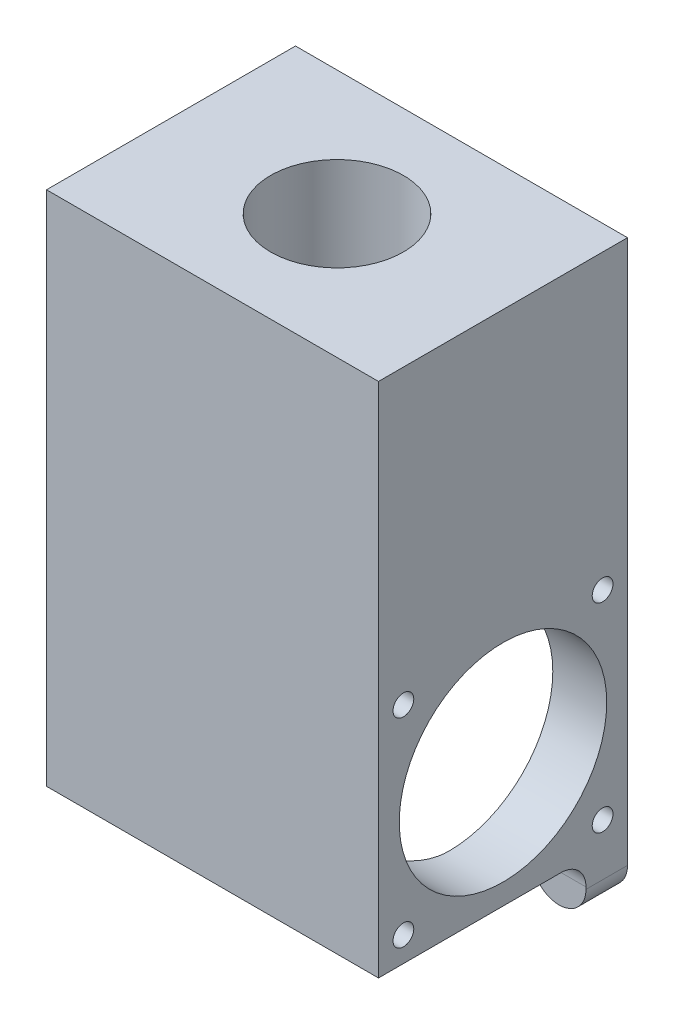
SolidWorks part; units mm, degrees
ref_plane "Спереди" through (0, 0, 0) normal (0, 0, 1) x (1, 0, 0)
ref_plane "Сверху" through (0, 0, 0) normal (0, 1, 0) x (1, 0, 0)
ref_plane "Справа" through (0, 0, 0) normal (1, 0, 0) x (0, 0, -1)
sketch "Эскиз1" plane through (0, 0, 0) normal (0, 0, 1) x (1, 0, 0)
  line L1 (20, -35.25) -> (-20, -35.25)
  line L2 (20, -35.25) -> (20, 35.25)
  line L3 (20, 35.25) -> (-20, 35.25)
  line L4 (-20, -35.25) -> (-20, 35.25)
  line L5 (20, -35.25) -> (-20, 35.25) construction
  line L6 (20, 35.25) -> (-20, -35.25) construction
  point P0 (0, 0)
  dimension "D1" = 40
  dimension "D2" = 70.5
extrude "Бобышка-Вытянуть1" add sketch "Эскиз1" along normal blind 30
sketch "Эскиз2" plane through (0, -35.25, 0) normal (0, -1, 0) x (1, 0, 0)
  line L0 (-20, 0) -> (20, 0) construction
  line L1 (-13.5, 15) -> (-13.5, 0)
  line L2 (-13.5, 0) -> (13.5, 0)
  line L3 (13.5, 0) -> (13.5, 15)
  arc A0 (13.5, 15) -> (-13.5, 15) centre (0, 15) ccw
  dimension "D1" = 27
  dimension "D2" = 15
extrude "Вырез-Вытянуть1" cut sketch "Эскиз2" against normal blind 46.05
ref_plane "Плоскость1" through (0, 0, 15) normal (0, 0, -1) x (-1, 0, 0)
sketch "Эскиз3" plane through (0, 0, 15) normal (0, 0, -1) x (-1, 0, 0)
  line L0 (0, 50.0613) -> (0, -61.5012) construction
  line L1 (0, 35.25) -> (0, 10.8)
  line L2 (0, 10.8) -> (-8, 10.8)
  line L3 (-8, 10.8) -> (-8, 13.8)
  line L4 (-8, 13.8) -> (-6, 13.8)
  line L5 (-6, 13.8) -> (-6, 19.4)
  line L6 (-6, 19.4) -> (-8, 19.4)
  line L7 (-8, 19.4) -> (-8, 35.25)
  line L8 (-8, 35.25) -> (0, 35.25)
  line L9 (-20, 35.25) -> (20, 35.25) construction
  line L10 (-13.5, -35.25) -> (-20, -35.25) construction
  line L11 (13.5, 10.8) -> (-13.5, 10.8) construction
  dimension "D1" = 16
  dimension "D2" = 12
  dimension "D3" = 49.05
  dimension "D4" = 5.6
revolve "Вырез-Повернуть1" cut sketch "Эскиз3" angle 360 about L0
sketch "Эскиз4" plane through (20, 0, 0) normal (1, 0, 0) x (0, 0, -1)
  line L0 (-5, -30) -> (-5, -33.5)
  line L1 (-30, -35.25) -> (0, -35.25) construction
  line L2 (-8, -27) -> (-30, -27)
  line L3 (-30, -35.25) -> (-30, 35.25) construction
  line L4 (-30, -27) -> (-30, -35.25)
  line L5 (-30, -35.25) -> (0, -35.25)
  line L7 (-5, -33.5) -> (0, -33.5)
  line L8 (0, -35.25) -> (0, 35.25) construction
  line L9 (0, -33.5) -> (0, -35.25)
  arc A0 (-5, -30) -> (-8, -27) centre (-8, -30) ccw
  dimension "D3" = 3
  dimension "D1" = 1.75
  dimension "D2" = 6.5
  dimension "D4" = 5
extrude "Вырез-Вытянуть2" cut sketch "Эскиз4" against normal blind 40
sketch "Эскиз5" plane through (20, 0, 0) normal (1, 0, 0) x (0, 0, -1)
  line L0 (0, -33.5) -> (0, 35.25) construction
  line L1 (-8, -27) -> (-30, -27) construction
  circle A0 centre (-15, -12) radius 12.5
  dimension "D3" = 25
  dimension "D1" = 15
  dimension "D2" = 15
extrude "Вырез-Вытянуть3" cut sketch "Эскиз5" against normal blind 40
sketch "Эскиз6" plane through (20, 0, 0) normal (1, 0, 0) x (0, 0, -1)
  line L1 (-27, -24) -> (-3, -24) construction
  line L2 (-27, -24) -> (-27, 0) construction
  line L3 (-27, 0) -> (-3, 0) construction
  line L4 (-3, -24) -> (-3, 0) construction
  line L5 (-27, -24) -> (-3, 0) construction
  line L6 (-27, 0) -> (-3, -24) construction
  circle A0 centre (-27, 0) radius 1.25
  circle A1 centre (-3, 0) radius 1.25
  circle A2 centre (-3, -24) radius 1.25
  circle A3 centre (-27, -24) radius 1.25
  point P0 (-15, -12)
  dimension "D2" = 2.5
  dimension "D1" = 24
extrude "Вырез-Вытянуть4" cut sketch "Эскиз6" against normal blind 6.5
fillet "Скругление1" radius 3.25 4 edges at (-20, -33.5, 2.5) (-13.5, -33.5, 2.5) (13.5, -33.5, 2.5) (20, -33.5, 2.5)
equation "\"D1@Вырез-Вытянуть1\"=6.5+1.75+50.1-12.3"
equation "\"D3@Эскиз3\"=6.5+1.75+50.1-9.3"
